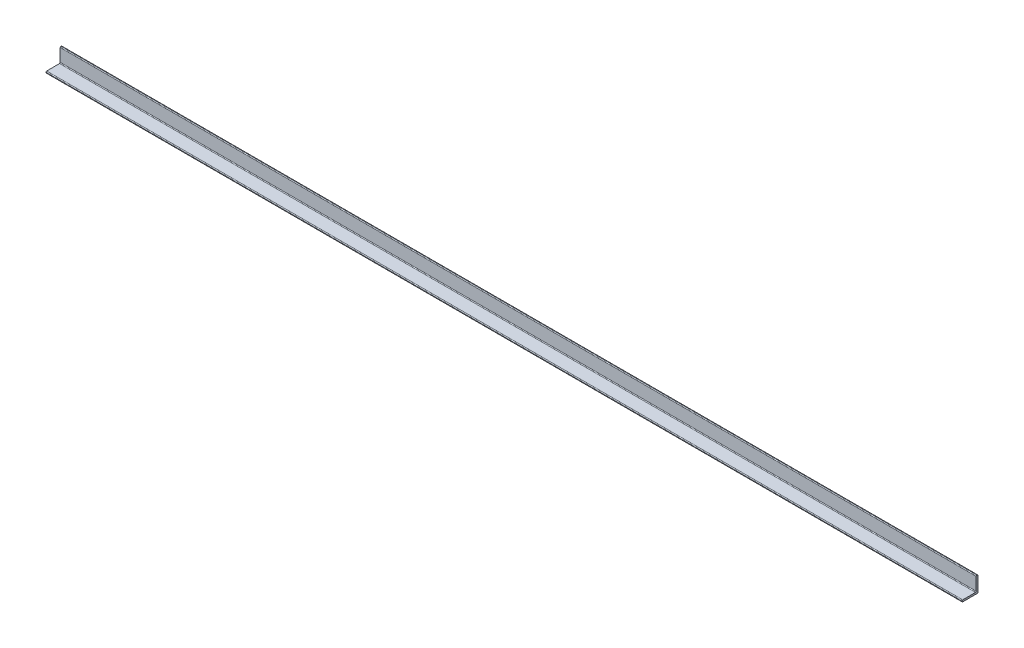
SolidWorks part; units mm, degrees
ref_plane "Front Plane" through (0, 0, 0) normal (0, 0, 1) x (1, 0, 0)
ref_plane "Top Plane" through (0, 0, 0) normal (0, 1, 0) x (1, 0, 0)
ref_plane "Right Plane" through (0, 0, 0) normal (1, 0, 0) x (0, 0, -1)
sketch "Sketch1" plane through (0, 0, 0) normal (0, 1, 0) x (1, 0, 0)
  line L1 (-644, 11.25) -> (644, 11.25)
  line L2 (-644, 11.25) -> (-644, -11.25)
  line L3 (-644, -11.25) -> (644, -11.25)
  line L4 (644, 11.25) -> (644, -11.25)
  line L5 (-644, 11.25) -> (644, -11.25) construction
  line L6 (-644, -11.25) -> (644, 11.25) construction
  point P0 (0, 0)
  dimension "D1" = 1288
  dimension "D2" = 22.5
extrude "Boss-Extrude1" add sketch "Sketch1" along normal blind 2.5
sketch "Sketch2" plane through (0, 2.5, 0) normal (0, 1, 0) x (1, 0, 0)
  line L0 (644, -11.25) -> (644, 11.25) construction
  line L1 (-644, 11.25) -> (644, 11.25)
  line L2 (-644, 11.25) -> (-644, 8.75)
  line L3 (-644, 8.75) -> (644, 8.75)
  line L4 (644, 11.25) -> (644, 8.75)
  dimension "D1" = 2.5
extrude "Boss-Extrude2" add sketch "Sketch2" along normal blind 20
fillet "Fillet1" radius 1 6 edges at (0, 0, -11.25) (0, 0, 11.25) (0, 2.5, 11.25) (0, 2.5, -8.75) (0, 22.5, -8.75) (0, 22.5, -11.25)
